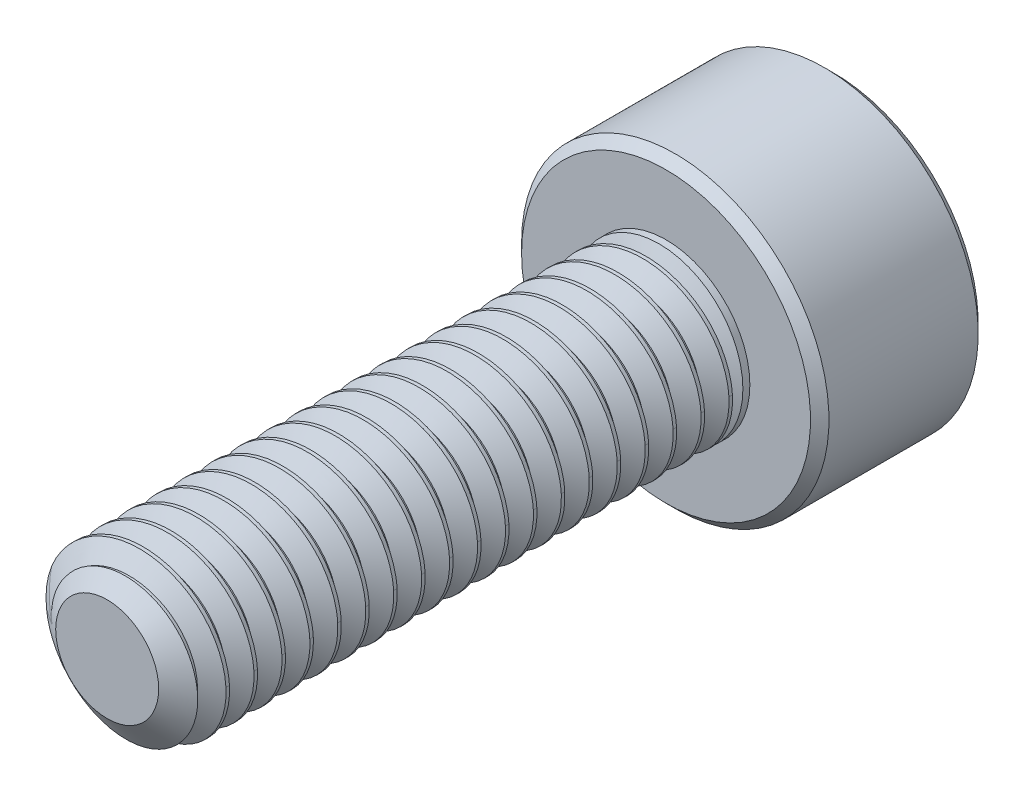
SolidWorks part; units mm, degrees
ref_plane "Front Plane" through (0, 0, 0) normal (0, 0, 1) x (1, 0, 0)
ref_plane "Top Plane" through (0, 0, 0) normal (0, 1, 0) x (1, 0, 0)
ref_plane "Right Plane" through (0, 0, 0) normal (1, 0, 0) x (0, 0, -1)
sketch "Sketch1" plane through (0, 0, 0) normal (0, 0, 1) x (1, 0, 0)
  circle A0 centre (0, 0) radius 1.5
  dimension "OD" = 3
extrude "Extrude1" add sketch "Sketch1" against normal blind 10
sketch "Sketch2" plane through (0, 0, 0) normal (0, 0, 1) x (1, 0, 0)
  circle A0 centre (0, 0) radius 1.5 construction
  circle A1 centre (0, 0) radius 1.5
curve "Helix/Spiral1" pitch 0.5 height 10.5 radius 1.5 centre (0, 0, 0) axis (0, 0, -1) start towards (0, 1, 0) parameters "pitch"=0.5
sketch "Sketch3" plane through (0, 0, 0) normal (1, 0, 0) x (0, 0, -1)
  line L0 (-0.4375, 1.5) -> (-0.25, 1.1752)
  line L1 (-0.25, 1.1752) -> (-0.1875, 1.1752)
  line L2 (-0.1875, 1.1752) -> (0, 1.5)
  line L3 (-0.4375, 1.5) -> (0, 1.5)
  line L4 (-0.2187, 1.5) -> (-0.2187, 1.1752) construction
  line L5 (-0.3437, 1.3376) -> (-0.0937, 1.3376) construction
  line L6 (0, 1.5) -> (0, -1.5) construction
  line L7 (0, -1.5) -> (10, -1.5) construction
  point P11 (2.25, -1.5)
  dimension "D1" = 0.0625
  dimension "D2" = 0.25
  dimension "D3" = 60
  dimension "D4" = 2.25
sweep "Cut-Sweep1" cut profiles "Sketch3" path "Helix/Spiral1"
sketch "Sketch4" plane through (0, 0, 0) normal (1, 0, 0) x (0, 0, -1)
  line L0 (0.4053, 1.5) -> (0, 0.9212)
  line L1 (0, 0.9212) -> (0, 1.5)
  line L2 (0.4053, 1.5) -> (0, 1.5)
  line L3 (-0.4375, 1.5) -> (0, 1.5) construction
  line L4 (0, 0) -> (7.0209, 0) construction
  dimension "D1" = 55
  dimension "D2" = 0.254
revolve "Cut-Revolve1" cut sketch "Sketch4" angle 360 about L4
sketch "Sketch5" plane through (0, 0, 0) normal (1, 0, 0) x (0, 0, -1)
  line L0 (10, -1.1822) -> (10, 1.0703) construction
  line L1 (10, 1.5) -> (0.1203, 1.5)
  line L2 (10, 1.5) -> (10, 0)
  line L3 (10, 0) -> (0.0001, 0)
  line L4 (0.0001, 1.1698) -> (0.0001, 0)
  line L5 (0.1203, 1.5) -> (0.0001, 1.1698)
  line L6 (0, 0) -> (9.9695, 0) construction
  point P3 (0.0001, 1.5)
  point P10 (0.0001, 1.5)
  dimension "D1" = 0.3302
  dimension "Thread min" = 0.0001
  dimension "D3" = 20
revolve "partially thread" [suppressed] add sketch "Sketch5" angle 360 about L6
sketch "Sketch6" plane through (0, 0, -10) normal (0, 0, -1) x (-1, 0, 0)
  circle A0 centre (0, 0) radius 2.75
  dimension "head dia" = 5.5
extrude "Extrude2" add sketch "Sketch6" along normal blind 3
sketch "Sketch7" plane through (0, 0, -13) normal (0, 0, -1) x (-1, 0, 0)
  line L1 (0, 1.4434) -> (-1.25, 0.7217)
  line L2 (-1.25, 0.7217) -> (-1.25, -0.7217)
  line L3 (-1.25, -0.7217) -> (0, -1.4434)
  line L4 (0, -1.4434) -> (1.25, -0.7217)
  line L5 (1.25, -0.7217) -> (1.25, 0.7217)
  line L6 (1.25, 0.7217) -> (0, 1.4434)
  circle A0 centre (0, 0) radius 1.25 construction
  dimension "hex dia" = 2.5
extrude "Cut-Extrude1" cut sketch "Sketch7" against normal blind 1.875
sketch "Sketch8" plane through (0, 0, -13) normal (0, 0, -1) x (-1, 0, 0)
  circle A0 centre (0, 0) radius 1.4434
extrude "Cut-Extrude2" cut sketch "Sketch8" against normal through all draft 45
chamfer "Chamfer1" distance 0.165 angle 45 2 edges at (-2.75, 0, -13) (-2.75, 0, -10)
sketch "Sketch9" plane through (0, 0, 0) normal (1, 0, 0) x (0, 0, -1)
  line L0 (0, 1.5) -> (0, -1.5) construction
  line L1 (2.75, 1.5) -> (2.75, -1.5) construction
  dimension "D1" = 2.75
sketch "Sketch10" plane through (0, 0, 0) normal (1, 0, 0) x (0, 0, -1)
  line L0 (10, 1.5) -> (10, 0)
  line L1 (10, 1.5) -> (9.875, 1.5)
  line L2 (9.875, 1.5) -> (9.2537, 0)
  line L3 (10, 0) -> (9.2537, 0)
  line L4 (10, 2.585) -> (10, -2.585) construction
  dimension "D1" = 22.5
  dimension "D2" = 0.125
revolve "Revolve1" add sketch "Sketch10" angle 360 about L3
equation "\"D3@Helix/Spiral1\" = \"screw length@Extrude1\"+\"pitch@Helix/Spiral1\""
equation "\"D1@Sketch3\" = \"pitch@Helix/Spiral1\"*.125"
equation "\"D2@Sketch3\" = \"pitch@Helix/Spiral1\"*.5"
equation "\"D1@Cut-Extrude1\" = \"hex dia@Sketch7\"*.75"
equation "\"D1@Chamfer1\" = \"head dia@Sketch6\"*.03"
equation "\"D1@Sketch9\" = \"pitch@Helix/Spiral1\"*5.5"
equation "\"D2@Sketch10\" = \"pitch@Helix/Spiral1\"*.25"
equation "\"D4@Sketch3\" = \"pitch@Helix/Spiral1\"*4.50"
